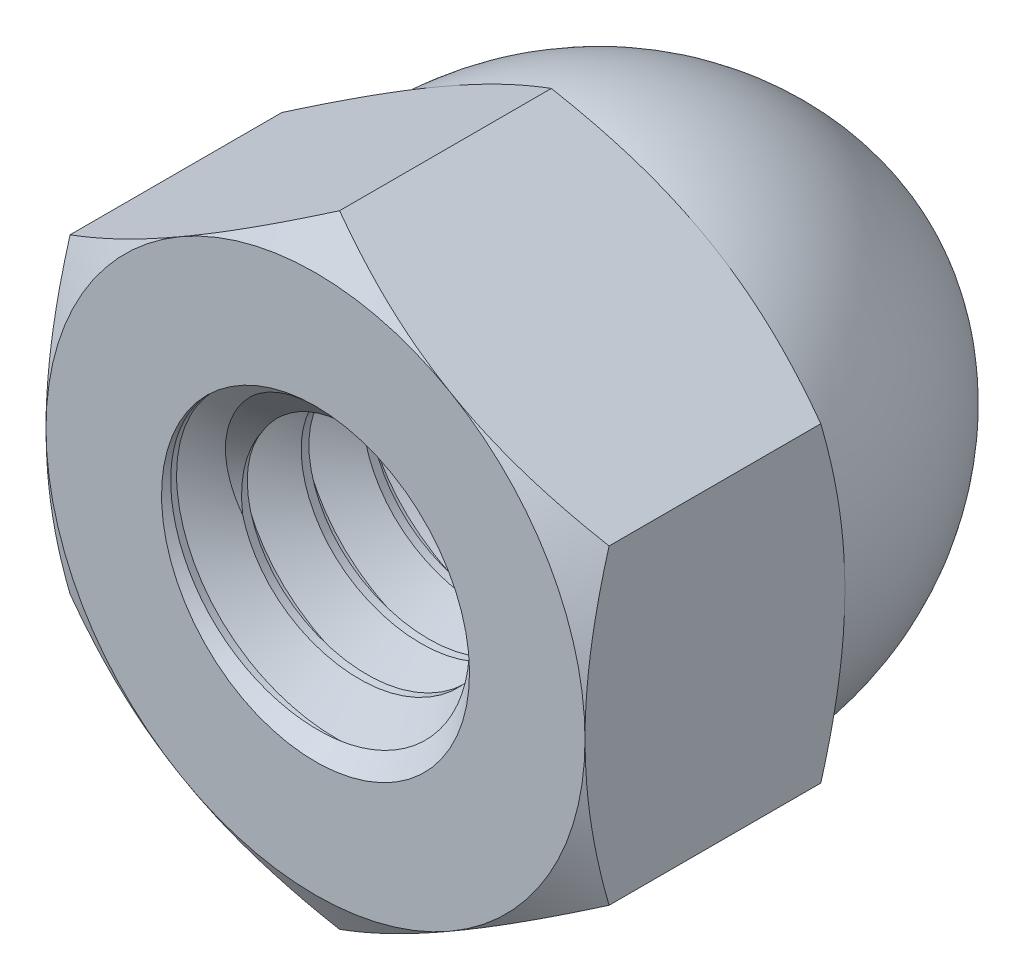
SolidWorks part; units mm, degrees
ref_plane "Front Plane" through (0, 0, 0) normal (0, 0, 1) x (1, 0, 0)
ref_plane "Top Plane" through (0, 0, 0) normal (0, 1, 0) x (1, 0, 0)
ref_plane "Right Plane" through (0, 0, 0) normal (1, 0, 0) x (0, 0, -1)
sketch "Sketch1" plane through (0, 0, 0) normal (0, 0, 1) x (1, 0, 0)
  line L1 (0, 6.4158) -> (-5.5563, 3.2079)
  line L2 (-5.5563, 3.2079) -> (-5.5563, -3.2079)
  line L3 (-5.5563, -3.2079) -> (0, -6.4158)
  line L4 (0, -6.4158) -> (5.5562, -3.2079)
  line L5 (5.5562, -3.2079) -> (5.5562, 3.2079)
  line L6 (5.5562, 3.2079) -> (0, 6.4158)
  circle A0 centre (0, 0) radius 5.5563 construction
  dimension "Hex" = 11.1125
extrude "Extrude1" add sketch "Sketch1" against normal blind 5.3578
sketch "Sketch2" plane through (0, 0, 0) normal (0, 0, 1) x (1, 0, 0)
  circle A0 centre (0, 0) radius 5.5563 construction
  circle A1 centre (0, 0) radius 5.5563
extrude "Cut-Extrude1" cut sketch "Sketch2" against normal through all draft 60 flip side to cut
sketch "Sketch3" plane through (0, 0, -5.3578) normal (0, 0, -1) x (-1, 0, 0)
  circle A1 centre (0, 0) radius 5.5563
  circle A2 centre (0, 0) radius 5.5563
  dimension "D1" = 0
extrude "Cut-Extrude2" cut sketch "Sketch3" against normal through all draft 60 flip side to cut
sketch "Sketch14" plane through (0, 0, 0) normal (1, 0, 0) x (0, 0, -1)
  line L0 (5.3578, 5.5563) -> (5.3578, 0)
  line L1 (5.3578, 0) -> (11.9062, 0)
  line L2 (5.3578, 0) -> (5.3578, 4.8119) construction
  line L3 (5.3578, 5.5563) -> (12.6759, 5.5563) construction
  line L6 (0, 0) -> (5.3578, 0) construction
  arc A0 (5.3578, 5.5563) -> (11.9062, 0) centre (5.3578, -1.0808) cw
  dimension "overall length" = 11.9062
revolve "Revolve1" add sketch "Sketch14" angle 360 about L6
sketch "Sketch4" plane through (0, 0, 0) normal (0, 0, 1) x (1, 0, 0)
  circle A0 centre (0, 0) radius 3.175
  dimension "Thread Dia" = 6.35
extrude "Cut-Extrude3" cut sketch "Sketch4" against normal blind 6.35
sketch "Sketch5" plane through (0, 0, 0) normal (0, 0, 1) x (1, 0, 0)
  circle A0 centre (0, 0) radius 3.175 construction
  circle A1 centre (0, 0) radius 3.175
sketch "Sketch15" plane through (0, 0, -6.35) normal (0, 0, 1) x (1, 0, 0)
  circle A0 centre (0, 0) radius 3.175 construction
  circle A1 centre (0, 0) radius 3.175
curve "Helix/Spiral2" pitch 1.27 height 9.525 turns 7.5 parameters "pitch"=1.27
sketch "Sketch18" plane through (0, 0, 0) normal (0, 0, 1) x (1, 0, 0)
  circle A0 centre (0, 0) radius 3.175 construction
  circle A1 centre (0, 0) radius 3.175
sketch "Sketch16" plane through (0, 0, 0) normal (1, 0, 0) x (0, 0, -1)
  line L0 (6.35, 3.175) -> (7.4612, 3.175)
  line L1 (7.4612, 3.175) -> (6.985, 2.3501)
  line L2 (6.985, 2.3501) -> (6.8262, 2.3501)
  line L3 (6.8262, 2.3501) -> (6.35, 3.175)
  line L4 (6.9056, 2.3501) -> (6.9056, 3.175) construction
  line L5 (6.5881, 2.7626) -> (7.2231, 2.7626) construction
  line L6 (6.35, 3.175) -> (6.35, -3.175) construction
  dimension "D1" = 60
  dimension "D2" = 0.1588
  dimension "D3" = 0.635
sweep "Sweep1" add profiles "Sketch16" path "Helix/Spiral2"
sketch "Sketch17" plane through (0, 0, 0) normal (0, 0, 1) x (1, 0, 0)
  line L6 (0, 6.4158) -> (-5.5563, 3.2079)
  line L7 (-5.5563, 3.2079) -> (-5.5563, -3.2079)
  line L8 (-5.5563, -3.2079) -> (0, -6.4158)
  line L9 (0, -6.4158) -> (5.5562, -3.2079)
  line L10 (5.5562, -3.2079) -> (5.5562, 3.2079)
  line L11 (5.5562, 3.2079) -> (0, 6.4158)
  line L12 (0, 6.4158) -> (-5.5563, 3.2079)
  line L13 (-5.5563, 3.2079) -> (-5.5563, -3.2079)
  line L14 (-5.5563, -3.2079) -> (0, -6.4158)
  line L15 (0, -6.4158) -> (5.5562, -3.2079)
  line L16 (5.5562, -3.2079) -> (5.5562, 3.2079)
  line L17 (5.5562, 3.2079) -> (0, 6.4158)
  dimension "D1" = 0
extrude "Cut-Extrude8" cut sketch "Sketch17" along normal through all
extrude "Cut-Extrude9" cut sketch "Sketch18" against normal through all draft 45
sketch "Sketch20" plane through (0, 0, 0) normal (1, 0, 0) x (0, 0, -1)
  line L0 (6.985, 3.175) -> (8.8181, 0)
  line L1 (6.35, 3.175) -> (6.985, 3.175)
  line L2 (6.35, 3.175) -> (6.35, 0)
  line L3 (6.35, 3.175) -> (7.4612, 3.175) construction
  line L4 (6.35, 3.175) -> (6.35, -3.175) construction
  line L5 (6.35, 0) -> (8.8181, 0)
  line L6 (0, 0) -> (-3.6507, 0) construction
  dimension "D1" = 0.635
  dimension "D2" = 60
revolve "Cut-Revolve1" cut sketch "Sketch20" angle 360 about L6
equation "\"D2@Sketch16\" = \"pitch@Helix/Spiral2\"*.125"
equation "\"D3@Sketch16\" = \"pitch@Helix/Spiral2\"*.50"
equation "\"D1@Sketch20\" = \"pitch@Helix/Spiral2\"/2"
equation "\"D3@Helix/Spiral2\" = \"Thread Depth@Cut-Extrude3\"+.125"
equation "\"Nut Height@Extrude1\" = \"overall length@Sketch14\"*.45"
